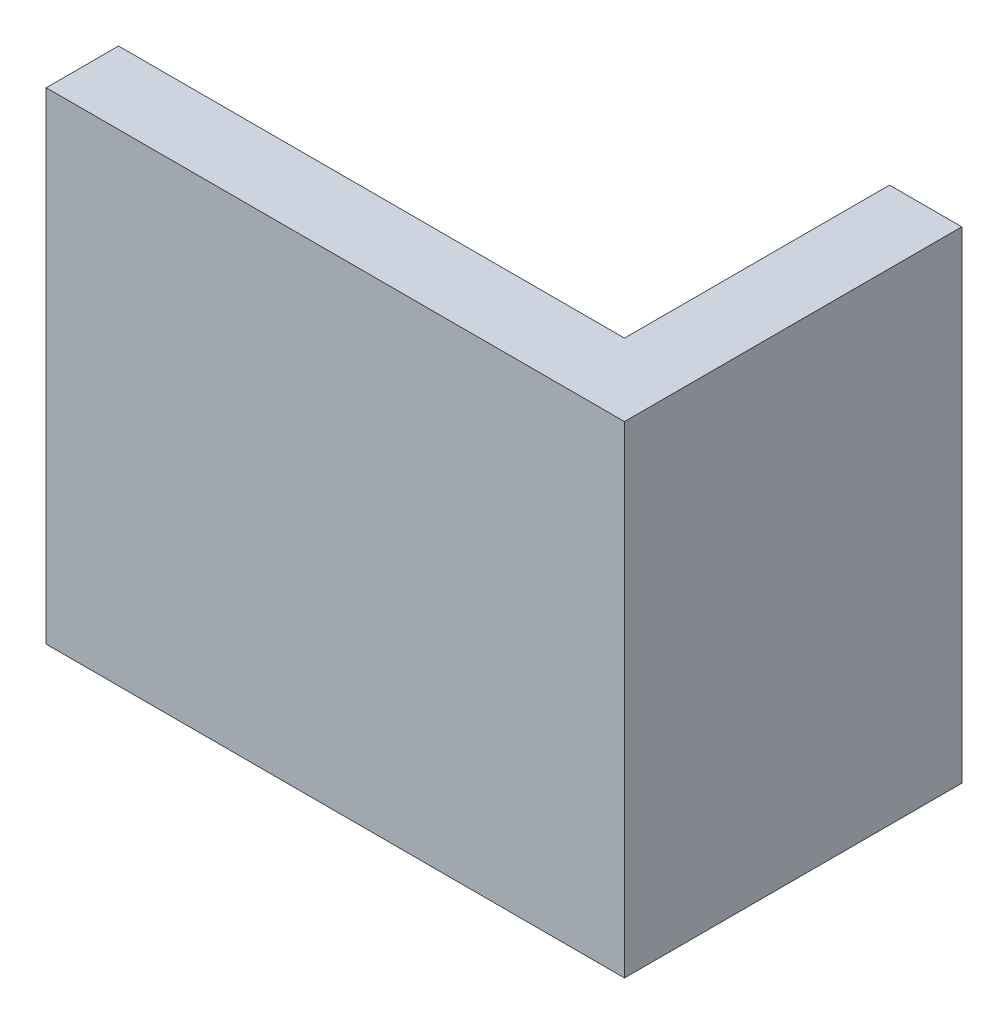
SolidWorks part; units mm, degrees
ref_plane "Front Plane" through (0, 0, 0) normal (0, 0, 1) x (1, 0, 0)
ref_plane "Top Plane" through (0, 0, 0) normal (0, 1, 0) x (1, 0, 0)
ref_plane "Right Plane" through (0, 0, 0) normal (1, 0, 0) x (0, 0, -1)
ref_axis "Axis1" through (-88.99, 0, 0) along (1, 0, 0)
sketch "Sketch1" plane through (0, 0, 0) normal (0, 1, 0) x (1, 0, 0)
  line L0 (9, -3) -> (9, 8)
  line L1 (-12, -6) -> (12, -6)
  line L2 (-12, -6) -> (-12, -3)
  line L3 (-12, -3) -> (9, -3)
  line L4 (12, -6) -> (12, 8)
  line L5 (9, 8) -> (12, 8)
  line L6 (0, -6) -> (0, 0) construction
  line L7 (-88.99, 0) -> (88.99, 0) construction
  dimension "D1" = 3
  dimension "D2" = 3
  dimension "D3" = 21
  dimension "D4" = 3
  dimension "D5" = 8
extrude "Boss-Extrude1" add sketch "Sketch1" along normal mid plane 20
